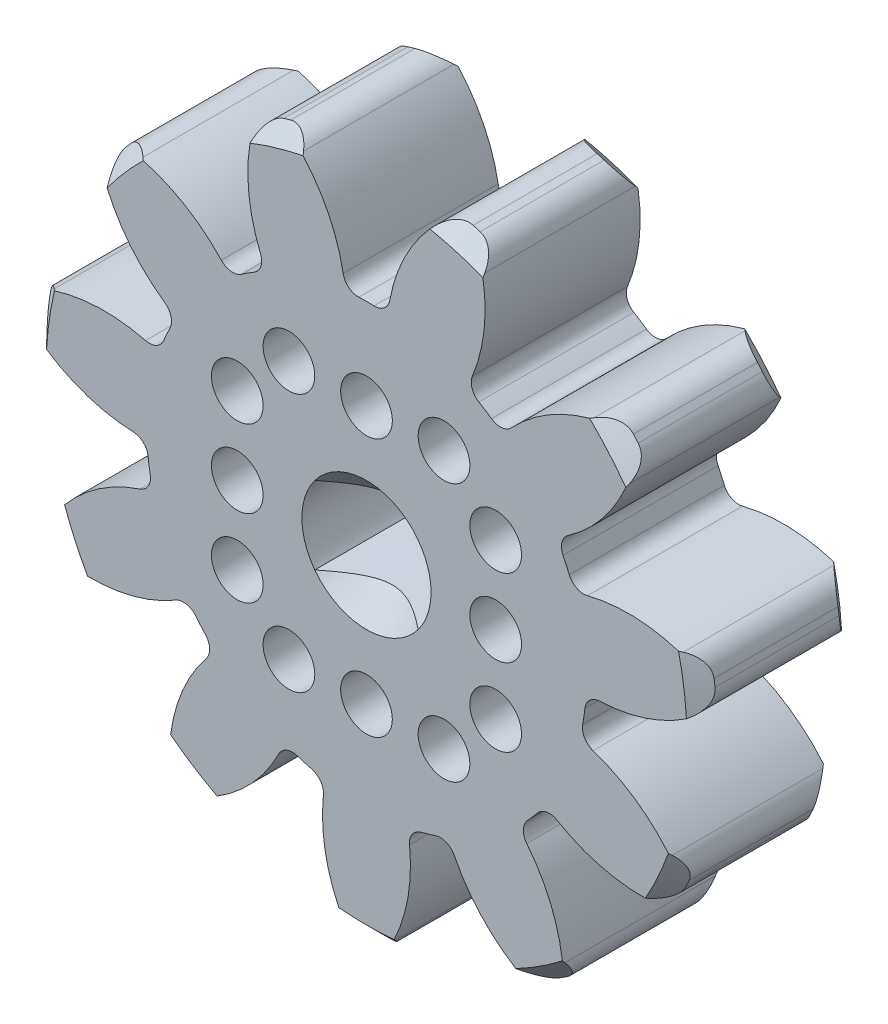
SolidWorks part; units mm, degrees
ref_plane "Front Plane" through (0, 0, 0) normal (0, 0, 1) x (1, 0, 0)
ref_plane "Top Plane" through (0, 0, 0) normal (0, 1, 0) x (1, 0, 0)
ref_plane "Right Plane" through (0, 0, 0) normal (1, 0, 0) x (0, 0, -1)
sketch "Sketch1" plane through (0, 0, 0) normal (0, 0, 1) x (1, 0, 0)
  circle A0 centre (0, 0) radius 8.5
  circle A1 centre (0, 0) radius 11
  circle A2 centre (0, 0) radius 13
  dimension "D1" = 22
  dimension "D2" = 17
  dimension "D3" = 26
extrude "Boss-Extrude1" add sketch "Sketch1" along normal blind 6 contours A2
sketch "Sketch2" plane through (0, 0, 0) normal (0, 0, 1) x (1, 0, 0)
  line L0 (0, 43.5968) -> (0, -43.5968) construction
  line L1 (-0.8282, 8.4596) -> (0, 0) construction
  line L2 (0.8282, 8.4596) -> (0, 0) construction
  line L3 (1.5655, 10.888) -> (-1.5655, 10.888) construction
  line L4 (-11.2564, 28.9753) -> (-6.0644, 19.2849) construction
  line L5 (-1.5655, 10.888) -> (7.7535, 15.881) construction
  line L6 (-1.5655, 10.888) -> (9.2435, 12.4421) construction
  line L7 (0, 0) -> (3.6625, 12.4734) construction
  line L8 (1.5655, 10.888) -> (4.5696, 10.006) construction
  arc A0 (-0.8282, 8.4596) -> (-2.9587, 12.6588) centre (-7.2763, 7.8282) ccw
  circle A1 centre (0, 0) radius 8.5 construction
  circle A2 centre (0, 0) radius 13 construction
  arc A3 (0.8282, 8.4596) -> (2.9587, 12.6588) centre (7.2763, 7.8282) cw
  arc A4 (0.8282, 8.4596) -> (-0.8282, 8.4596) centre (0, 0) ccw
  circle A5 centre (0, 0) radius 11 construction
  arc A7 (3.6625, 12.4734) -> (-2.9587, 12.6588) centre (0, 0) ccw
  point P4 (0, 0)
  point P14 (-1.5655, 10.888)
  point P16 (1.5655, 10.888)
  dimension "D1" = 20
  dimension "D2" = 16.364
extrude "Cut-Extrude1" cut sketch "Sketch2" along normal through all contours A3 A7 A0 A4 region at (0, 11.1941, 0)
fillet "Fillet1" radius 0.6 2 edges at (-0.8282, 8.4596, 3) (0.8282, 8.4596, 3)
chamfer "Chamfer1" distance 0.6 angle 45 2 edges at (0, -13, 0) (0, -13, 6)
pattern_circular "CirPattern1" count 11 over 360 about axis through (0, 0, 6) along (0, 0, -1) of "Cut-Extrude1", "Fillet1" reverse direction yes
sketch "Sketch3" plane through (0, 0, 0) normal (0, 0, 1) x (1, 0, 0)
  circle A0 centre (0, 0) radius 7.5
  dimension "D1" = 15
extrude "Cut-Extrude2" [suppressed] cut sketch "Sketch3" along normal through all
sketch "Sketch5" plane through (0, 0, 0) normal (1, 0, 0) x (0, 0, -1)
  line L1 (-6, 2.5) -> (-6, 0)
  line L2 (-6, 0) -> (0, 0) construction
  line L3 (0, 0) -> (0, 1.5)
  line L4 (0, 3.2642) -> (0, 3.7937) construction
  line L5 (-6, 8.8987) -> (-6, 7.2813) construction
  line L6 (-6, 2.5) -> (-5, 1.5)
  line L7 (-5, 1.5) -> (0, 1.5)
  line L9 (0, 0) -> (-6, 0)
  dimension "D1" = 3
  dimension "D2" = 5
  dimension "D3" = 45
revolve "Screw_cut" cut sketch "Sketch5" angle 360 about L2
sketch "Sketch6" plane through (0, 0, 0) normal (1, 0, 0) x (0, 0, -1)
  line L0 (0, 4.75) -> (-6, 4.75)
  line L1 (-6, 4.75) -> (-6, 0)
  line L2 (-6, 0) -> (0, 0) construction
  line L3 (0, 0) -> (0, 4.75)
  line L4 (0, -1.5) -> (0, 1.5) construction
  line L5 (-6, 2.5) -> (-6, -2.5) construction
  line L6 (-6, 0) -> (0, 0)
  dimension "D1" = 9.5
revolve "Hole_cut" [suppressed] cut sketch "Sketch6" angle 360 about L2
ref_axis "Axis1" through (0, 0, 6) along (0, 0, -1)
sketch "Sketch7" plane through (0, 0, 0) normal (0, 0, -1) x (-1, 0, 0)
  circle A0 centre (0, 0) radius 4.5
  dimension "D1" = 9
extrude "Cut-Extrude3" [suppressed] cut sketch "Sketch7" against normal through all
sketch "Sketch8" plane through (0, 0, 0) normal (0, 0, 1) x (1, 0, 0)
  circle A2 centre (0, -5) radius 1
  circle A3 centre (3, -5) radius 1
  circle A4 centre (-3, -5) radius 1
  dimension "D1" = 5
  dimension "D2" = 2
  dimension "D3" = 3
  dimension "D4" = 3
  dimension "D5" = 2
extrude "Cut-Extrude4" cut sketch "Sketch8" along normal through all contours A3 | A2 | A4
pattern_circular "CirPattern2" count 4 over 360 about axis through (0, 0, 6) along (0, 0, -1) of "Cut-Extrude4"
fillet "Fillet2" radius 1 22 edges at (-2.9587, 12.6588, 3) (2.9587, 12.6588, 3) (4.3548, 12.2489, 3) (9.3329, 9.0497, 3) (10.2858, 7.95, 3) (12.744, 2.5673, 3) (12.9511, 1.1271, 3) (12.1089, -4.7302, 3) (11.5045, -6.0537, 3) (7.6294, -10.5258, 3) (6.4053, -11.3125, 3) (0.7275, -12.9796, 3) (-0.7275, -12.9796, 3) (-6.4053, -11.3125, 3) (-7.6294, -10.5258, 3) (-11.5045, -6.0537, 3) (-12.1089, -4.7302, 3) (-12.9511, 1.1271, 3) (-12.744, 2.5673, 3) (-10.2858, 7.95, 3) (-9.3329, 9.0497, 3) (-4.3548, 12.2489, 3)
sketch "Sketch9" plane through (0, 0, 0) normal (0, 0, 1) x (1, 0, 0)
  line L0 (-2, 1.5) -> (2, 1.5)
  line L1 (-2, -1.5) -> (2, -1.5)
  line L2 (0, 1.5) -> (0, -1.5)
  circle A0 centre (0, 0) radius 2.5
  point P9 (0, 0)
  dimension "D1" = 3
  dimension "D2" = 5
extrude "Cut-Extrude5" cut sketch "Sketch9" along normal through all contours L0 A0 L1 L2 | L1 A0 L0 L2 region at (-1.1749, 0, 0) region at (1.1749, 0, 0)
sketch "Sketch10" [suppressed] plane through (0, 0, 0) normal (0, 0, -1) x (-1, 0, 0)
  circle A0 centre (0, 0) radius 9.75
  circle A1 centre (0, 0) radius 4.75 construction
  circle A2 centre (0, 0) radius 4.75
  dimension "D1" = 5
extrude "Boss-Extrude2" [suppressed] add sketch "Sketch10" along normal blind 7
equation "\"module\"= 2"
equation "\"No_teeth\"= 11"
equation "\"Pressure_angle\"= 20"
equation "\"add\"= \"module\""
equation "\"ded\"= \"module\" * 1.25"
equation "\"pitch_dia\"= \"module\" * \"No_teeth\""
equation "\"outer_dia\"= \"pitch_dia\" + 2 * \"add\""
equation "\"root_dia\"= \"pitch_dia\" - 2 * \"ded\""
equation "\"D2@Sketch1\"=\"root_dia\""
equation "\"D1@Sketch1\"=\"pitch_dia\""
equation "\"D3@Sketch1\"=\"outer_dia\""
equation "\"D1@Sketch2\"=\"Pressure_angle\""
equation "\"D2@Sketch2\"=180 / \"No_teeth\""
equation "\"D1@Chamfer1\"=\"module\" * 0.3"
equation "\"D1@CirPattern1\"=\"No_teeth\""
